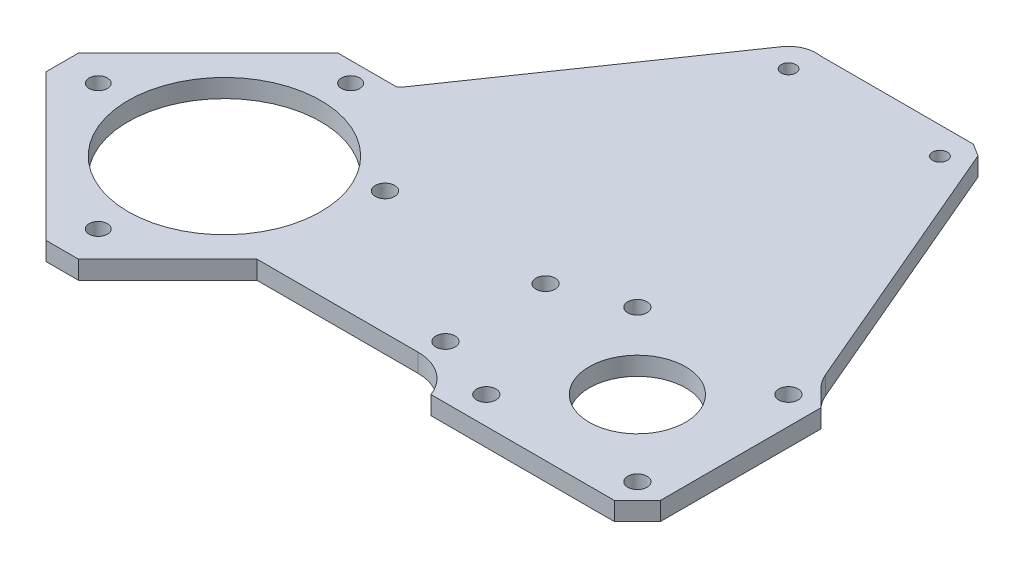
SolidWorks part; units mm, degrees
ref_plane "前视基准面" through (0, 0, 0) normal (0, 0, 1) x (1, 0, 0)
ref_plane "上视基准面" through (0, 0, 0) normal (0, 1, 0) x (1, 0, 0)
ref_plane "右视基准面" through (0, 0, 0) normal (1, 0, 0) x (0, 0, -1)
sketch "草图1" plane through (0, 0, 0) normal (0, 1, 0) x (1, 0, 0)
  line L0 (0, 0) -> (-31.8198, 0) construction
  line L1 (0, 31.8198) -> (-31.8198, 0)
  line L2 (-31.8198, 0) -> (0, -31.8198)
  line L3 (0, -31.8198) -> (15.9099, -15.9099)
  line L4 (15.9099, 15.9099) -> (0, 31.8198)
  line L5 (0, 0) -> (90, 0) construction
  line L6 (0, 0) -> (45, 77.9423) construction
  line L7 (45, 77.9423) -> (90, 0) construction
  line L8 (15.9099, 15.9099) -> (67.5, 15.9099)
  line L9 (15.9099, -15.9099) -> (67.5, -15.9099)
  line L10 (90, 0) -> (67.5, -22.5) construction
  line L11 (67.5, 22.5) -> (67.5, 15.9099)
  line L12 (67.5, -22.5) -> (112.5, -22.5)
  line L13 (112.5, -22.5) -> (112.5, 22.5)
  line L14 (112.5, 22.5) -> (67.5, 22.5)
  line L15 (67.5, -15.9099) -> (67.5, -22.5)
  line L16 (0, 0) -> (15.9099, 15.9099) construction
  line L17 (0, 0) -> (15.9099, -15.9099) construction
  circle A0 centre (0, 14) radius 2.1
  circle A1 centre (14, 0) radius 2.1
  circle A2 centre (0, -14) radius 2.1
  circle A3 centre (-14, 0) radius 2.1
  circle A4 centre (0, 0) radius 22.5 construction
  arc A5 (45, -77.9423) -> (45, 77.9423) centre (0, 0) ccw construction
  arc A6 (45, 77.9423) -> (45, -77.9423) centre (90, 0) ccw construction
  circle A7 centre (90, 0) radius 10.5
  circle A8 centre (90, 0) radius 22.5 construction
  circle A9 centre (0, 22.5) radius 2.1
  circle A11 centre (0, -22.5) radius 2.1
  circle A12 centre (0, 0) radius 10
  circle A13 centre (0, 0) radius 14 construction
  circle A14 centre (-22.5, 0) radius 2.1
  dimension "D1" = 4.2
  dimension "D2" = 20
  dimension "D3" = 4.2
  dimension "D4" = 4.2
  dimension "D5" = 4.2
  dimension "D6" = 45
  dimension "D9" = 180
  dimension "D10" = 180
  dimension "D11" = 21
  dimension "D14" = 4.2
  dimension "D15" = 4.2
  dimension "D17" = 4.2
  dimension "D7" = 180
  dimension "D8" = 90
  dimension "D12" = 135
  dimension "D13" = 45
extrude "凸台-拉伸1" add sketch "草图1" along normal blind 4
chamfer "倒角1" distance 5 angle 45 5 edges at (112.5, 2, 22.5) (112.5, 2, -22.5) (0, 2, 31.8198) (-31.8198, 2, 0) (0, 2, -31.8198)
fillet "圆角1" radius 10 4 edges at (15.9099, 2, -15.9099) (15.9099, 2, 15.9099) (67.5, 2, 15.9099) (67.5, 2, -15.9099)
sketch "草图2" plane through (0, 0, 0) normal (0, -1, 0) x (1, 0, 0)
  line L0 (39.0757, 15.9099) -> (39.0757, 10.9099) construction
  line L1 (20.052, 15.9099) -> (58.0993, 15.9099) construction
  line L2 (39.0757, 10.9099) -> (24.0757, 10.9099) construction
  line L3 (39.0757, 10.9099) -> (59.0757, 10.9099) construction
  line L4 (110, 20) -> (90, 0) construction
  line L5 (112.5, 17.5) -> (107.5, 22.5) construction
  line L6 (110, -20) -> (90, 0) construction
  line L7 (107.5, -22.5) -> (112.5, -17.5) construction
  line L8 (90, 22.5) -> (90, -22.5) construction
  line L9 (67.5, 22.5) -> (107.5, 22.5) construction
  line L10 (107.5, -22.5) -> (67.5, -22.5) construction
  line L11 (70, -20) -> (90, 0) construction
  line L12 (70, 20) -> (90, 0) construction
  line L13 (0, 0) -> (90, 0) construction
  line L14 (39.0757, -10.9099) -> (59.0757, -10.9099) construction
  line L15 (39.0757, -10.9099) -> (24.0757, -10.9099) construction
  line L16 (39.0757, -15.9099) -> (39.0757, -10.9099) construction
  circle A0 centre (106.4645, 16.4645) radius 2.1
  circle A1 centre (106.4645, -16.4645) radius 2.1
  circle A2 centre (73.5355, -16.4645) radius 2.1
  circle A3 centre (73.5355, 16.4645) radius 2.1
  circle A4 centre (24.0757, 10.9099) radius 2.1
  circle A5 centre (59.0757, 10.9099) radius 2.1
  circle A6 centre (59.0757, -10.9099) radius 2.1
  circle A7 centre (24.0757, -10.9099) radius 2.1
  dimension "D3" = 4.2
  dimension "D4" = 4.2
  dimension "D5" = 20
  dimension "D6" = 15
  dimension "D8" = 4.2
  dimension "D9" = 4.2
  dimension "D1" = 5
  dimension "D2" = 5
  dimension "D7" = 5
extrude "切除-拉伸1" cut sketch "草图2" against normal blind 10
sketch "草图3" plane through (0, 4, 0) normal (0, 1, 0) x (1, 0, 0)
  line L0 (0, 0) -> (90, 0) construction
  line L1 (45, 0) -> (45, 77.9423) construction
  line L2 (3.5355, 28.2843) -> (40.0576, 81.3442)
  line L3 (67.5, 22.5) -> (50.7578, 79.6297)
  line L4 (12.981, 18.8388) -> (3.5355, 28.2843) construction
  line L5 (58.0993, 15.9099) -> (20.052, 15.9099) construction
  line L6 (12.981, 18.8388) -> (3.5355, 28.2843)
  line L7 (58.0993, 15.9099) -> (20.052, 15.9099)
  line L8 (16.4918, 29.4702) -> (43.5266, 68.7468)
  line L9 (56.0801, 25.9099) -> (43.5266, 68.7468)
  line L10 (56.0801, 25.9099) -> (20.052, 25.9099)
  line L11 (20.052, 25.9099) -> (16.4918, 29.4702)
  circle A0 centre (45, 77.9423) radius 1.6
  arc A1 (50.7578, 79.6297) -> (40.0576, 81.3442) centre (45, 77.9423) ccw
  arc A2 (12.981, 18.8388) -> (20.052, 15.9099) centre (20.052, 25.9099) ccw construction
  arc A3 (58.0993, 15.9099) -> (67.5, 22.5) centre (58.0993, 25.9099) ccw construction
  arc A4 (12.981, 18.8388) -> (20.052, 15.9099) centre (20.052, 25.9099) ccw
  arc A5 (58.0993, 15.9099) -> (67.5, 22.5) centre (58.0993, 25.9099) ccw
  arc A6 (43.5266, 68.7468) -> (43.5266, 68.7468) centre (43.5266, 68.7468) ccw
  arc A7 (56.0801, 25.9099) -> (56.0801, 25.9099) centre (56.0801, 25.9099) ccw
  arc A8 (20.052, 25.9099) -> (20.052, 25.9099) centre (20.052, 25.9099) ccw
  dimension "D1" = 3.2
  dimension "D2" = 12
  dimension "D3" = 10
extrude "凸台-拉伸2" add sketch "草图3" against normal blind 4
fillet "圆角2" radius 3 4 edges at (20.052, 2, -25.9099) (16.4918, 2, -29.4702) (56.0801, 2, -25.9099) (43.5266, 2, -68.7468)
fillet "圆角3" radius 11 2 edges at (3.5355, 2, -28.2843) (67.5, 2, -22.5)
sketch "草图4" plane through (0, 4, 0) normal (0, 1, 0) x (1, 0, 0)
  line L0 (45.9493, 83.8667) -> (81.3477, 83.8667)
  line L3 (81.3477, 83.8667) -> (107.5, 22.5)
  line L4 (52.1537, 74.8667) -> (75.4, 74.8667)
  line L5 (75.4, 74.8667) -> (97.7168, 22.5)
  line L6 (107.5, 22.5) -> (75.739, 22.5) construction
  line L7 (73.0682, 80.3383) -> (99.2205, 18.9716) construction
  line L8 (45.9493, 74.8667) -> (90, 74.8667) construction
  line L9 (107.5, 22.5) -> (97.7168, 22.5)
  line L10 (65.183, 30.4065) -> (50.7578, 79.6297) construction
  line L11 (52.1537, 74.8667) -> (50.7578, 79.6297)
  line L12 (45.9493, 83.8667) -> (90, 83.8667) construction
  arc A0 (50.7578, 79.6297) -> (40.0576, 81.3442) centre (45, 77.9423) ccw construction
  circle A2 centre (78, 77.9423) radius 1.6
  arc A3 (50.7578, 79.6297) -> (45.9493, 83.8667) centre (45, 77.9423) ccw
  dimension "D1" = 33
extrude "凸台-拉伸3" add sketch "草图4" against normal blind 4
fillet "圆角4" radius 10 3 edges at (75.4, 2, -74.8667) (97.7168, 2, -22.5) (52.1537, 2, -74.8667)
chamfer "倒角2" distance 2 angle 32 1 edges at (81.3477, 2, -83.8667) first distance on face at (63.6485, 2, -83.8667)
fillet "圆角5" radius 10 1 edges at (107.5, 2, -22.5)
sketch "草图5" plane through (0, 4, 0) normal (0, 1, 0) x (1, 0, 0)
  circle A0 centre (0, 0) radius 17.5
  dimension "D1" = 35
extrude "切除-拉伸2" cut sketch "草图5" against normal blind 10
sketch "草图7" plane through (0, 4, 0) normal (0, 1, 0) x (1, 0, 0)
  line L0 (12.981, -18.8388) -> (-3.3995, -35.2193)
  line L1 (-3.5355, -28.2843) -> (-37.7489, 5.9291)
  line L2 (-3.5355, 28.2843) -> (-39.0544, -7.2346)
  line L3 (-28.2843, -3.5355) -> (7.2456, -39.0654)
  line L4 (17.2701, -21.6208) -> (-7.4124, -46.3033)
  line L5 (3.0511, -41.942) -> (-42.1231, 3.2322)
  line L6 (-5.4464, 33.4445) -> (-45.5855, -6.6946)
  line L7 (-3.5355, 28.2843) -> (-12.521, 37.2698)
  line L8 (-7.0711, 31.8198) -> (5.8328, 31.8198)
  line L9 (17.2701, -21.6208) -> (30.0716, -8.8193)
  line L10 (5.8328, 31.8198) -> (30.0716, -8.8193)
  line L11 (0, 22.5) -> (0, -22.5)
  line L12 (0, -22.5) -> (0, 40.9067)
  line L13 (0, -22.5) -> (0, -38.8909)
  line L15 (-35.3553, 3.5355) -> (-35.3553, -3.5355)
  line L17 (-3.5355, -35.3553) -> (3.5355, -35.3553)
  arc A0 (-2.2469, 28.2843) -> (6.8141, 33.0474) centre (-2.2469, 39.2843) ccw construction
  circle A7 centre (0, 0) radius 19.5284
  dimension "D1" = 5
  dimension "D2" = 5
  dimension "D3" = 5
extrude "凸台-拉伸9" add sketch "草图7" against normal blind 4 contours A7 L11 L13 L3 L4 L9 L10 L8 L12 | A7 L11 L12 L8 L7 L2 L1 L3 L13 | L2 L7 L6 L1 | L1 L15 L2 | L5 L17 L13 L3 L1 L2 | L13 L17 L3 region at (-17.2317, 4, 18.1236) region at (-15.4068, 4, 15.4068) region at (0.736, 4, 27.1599) region at (1.1785, 4, 34.1768) region at (-34.1768, 4, 0) region at (-19.4454, 4, -15.9099)
sketch "草图9" plane through (0, 4, 0) normal (0, 1, 0) x (1, 0, 0)
  line L0 (0, 29.7102) -> (0, -45.2616)
  line L1 (0, 0) -> (-45.2704, 0)
  circle A0 centre (0, 0) radius 21
  circle A1 centre (0, 27.5) radius 2
  circle A2 centre (-27.5, 0) radius 2
  circle A3 centre (0, -27.5) radius 2
  circle M20 centre (0, 0) radius 17.5
  dimension "D1" = 42
  dimension "D2" = 4
  dimension "D3" = 4
  dimension "D4" = 4
  dimension "D5" = 27.5
  dimension "D6" = 27.5
  dimension "D7" = 27.5
extrude "凸台-拉伸10" add sketch "草图9" against normal blind 8 separate body contours L0 A1 | L0 A1 | L0 A0 M20 | L0 A0 L1 M20 | L1 A0 L0 M20 | L0 L1 M20 | L1 L0 M20 | L0 M20 | L1 A2 | L1 A2 | L0 A3 | L0 A3 region at (0.8488, 4, -27.5) region at (0.8488, 4, 27.5) region at (-0.8488, 4, 27.5) region at (-27.5, 4, 0.8488) region at (-27.5, 4, -0.8488) region at (14.5172, 4, -14.5172) region at (-0.297, 4, -19.25) region at (-0.8488, 4, -27.5) region at (7.4272, 4, 0) region at (-7.4272, 4, -7.4272) region at (-19.25, 4, 0.297) region at (-7.4272, 4, 7.4272)
combine bodies "组合1" operation type subtract main body 116 bodies to subtract 117 118 119 120
sketch "草图10" plane through (0, 4, 0) normal (0, 1, 0) x (1, 0, 0)
  line L0 (64.8604, 78.786) -> (37.2906, 66.3898)
  line L1 (37.2906, 66.3898) -> (10.816, 26.6997)
  line L2 (10.816, 26.6997) -> (34.2034, 14.4252)
  line L3 (34.2034, 14.4252) -> (66.6044, 20.5624)
  line L4 (66.6044, 20.5624) -> (97.5372, 20.5624)
  line L5 (97.5372, 20.5624) -> (99.1133, 32.8789)
  line L6 (99.1133, 32.8789) -> (78.415, 73.5772)
  line L7 (78.415, 73.5772) -> (64.8604, 78.786)
extrude "凸台-拉伸11" add sketch "草图10" against normal blind 4
